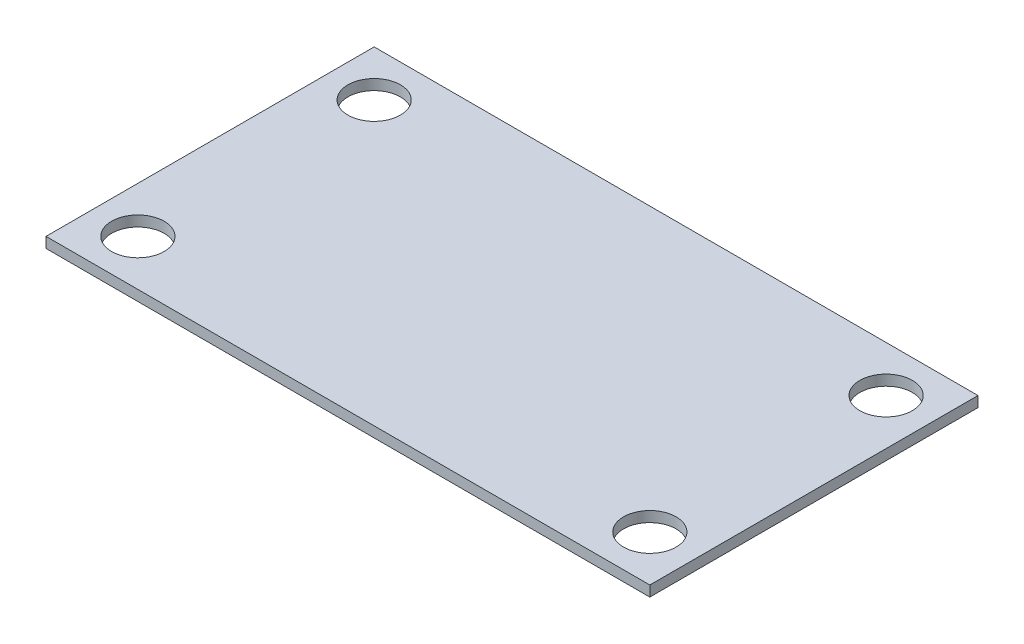
SolidWorks part; units mm, degrees
ref_plane "前视基准面" through (0, 0, 0) normal (0, 0, 1) x (1, 0, 0)
ref_plane "上视基准面" through (0, 0, 0) normal (0, 1, 0) x (1, 0, 0)
ref_plane "右视基准面" through (0, 0, 0) normal (1, 0, 0) x (0, 0, -1)
other "Configuration Table"
sketch "草图1" plane through (0, 0, 0) normal (0, 1, 0) x (1, 0, 0)
  line L0 (-46, 0) -> (46.2143, 0) construction
  line L1 (-46, 25) -> (46, 25)
  line L2 (-46, 25) -> (-46, -25)
  line L3 (-46, -25) -> (46, -25)
  line L4 (46, 25) -> (46, -25)
  line L7 (0, 25) -> (0, -30.3232) construction
  circle A2 centre (-39, -18) radius 4
  circle A3 centre (39, -18) radius 4
  circle A4 centre (39, 18) radius 4
  circle A5 centre (-39, 18) radius 4
  dimension "D3" = 7
  dimension "D4" = 8
  dimension "D1" = 50
  dimension "D2" = 92
  dimension "D5" = 7
extrude "凸台-拉伸1" add sketch "草图1" along normal blind 1.6
